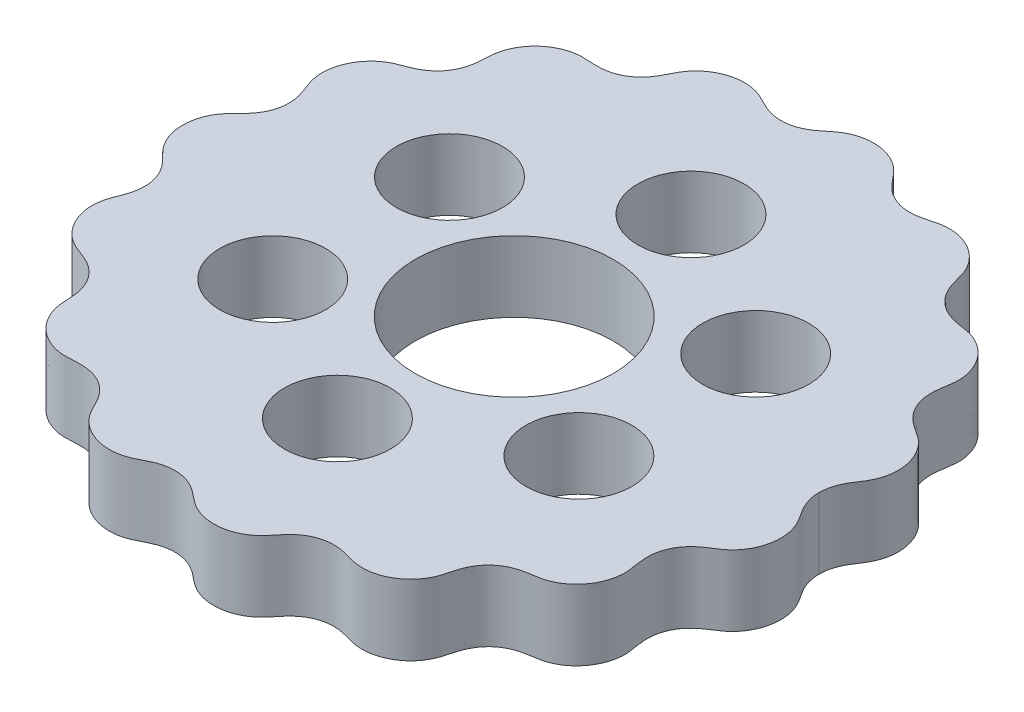
SolidWorks part; units mm, degrees
ref_plane "Front Plane" through (0, 0, 0) normal (0, 0, 1) x (1, 0, 0)
ref_plane "Top Plane" through (0, 0, 0) normal (0, 1, 0) x (1, 0, 0)
ref_plane "Right Plane" through (0, 0, 0) normal (1, 0, 0) x (0, 0, -1)
sketch "Sketch1" plane through (0, 0, 0) normal (0, 1, 0) x (1, 0, 0)
  spline S0 degree 4 poles (44.5984, 12.4944) (44.832, 12.1879) (45.2512, 11.5384) (45.7237, 10.4856) (45.9984, 9.1724) (46.03, 8.0346) (45.9105, 7.0216) (45.7203, 6.2632) (45.4573, 5.5829) (45.1464, 4.9823) (44.8648, 4.5205) (44.5648, 4.0709) (44.2669, 3.6199) (44.0083, 3.1913) (43.7929, 2.7844) (43.6185, 2.4022) (43.4802, 2.0484) (43.3629, 1.687) (43.2797, 1.3651) (43.2227, 1.0859) (43.1851, 0.8518) (43.1609, 0.6624) (43.145, 0.4992) (43.1351, 0.3578) (43.1294, 0.2322) (43.1264, 0.1298) (43.1245, 0.0125) (43.1252, -0.0782) (43.1286, -0.2195) (43.135, -0.3523) (43.1419, -0.4548) (43.1529, -0.582) (43.1699, -0.7377) (43.1951, -0.92) (43.231, -1.126) (43.274, -1.3311) (43.3366, -1.5852) (43.4549, -1.9872) (43.66, -2.5262) (44.0033, -3.2085) (44.4867, -3.963) (45.0117, -4.7244) (45.4649, -5.567) (45.8298, -6.5835) (46.0376, -7.77) (46.0189, -9.1082) (45.6992, -10.542) (45.1324, -11.7906) (44.3914, -12.8211) (43.5537, -13.6249) (42.6868, -14.2187) (41.8472, -14.7237) (41.113, -15.2701) (40.3565, -15.9849) (39.644, -16.9209) (39.0655, -18.1762) (38.8218, -19.6149) (38.8837, -20.8087) (39.0365, -21.7287) (39.15, -22.395) (39.2185, -22.9317) (39.2565, -23.6072) (39.2077, -24.5293) (38.9566, -25.6753) (38.3836, -26.9664) (37.4913, -28.188) (36.4562, -29.1122) (35.3715, -29.7513) (34.3004, -30.1449) (33.2968, -30.3406) (32.3424, -30.4567) (31.4554, -30.643) (30.6507, -30.9105) (29.9366, -31.2505) (29.1129, -31.7819) (28.2521, -32.581) (27.6169, -33.5017) (27.1961, -34.4634) (26.9571, -35.2233) (26.8167, -35.7523) (26.6832, -36.2827) (26.5312, -36.8085) (26.2971, -37.4517) (25.8833, -38.2906) (25.1883, -39.2563) (24.1248, -40.2304) (22.7782, -41.008) (21.4029, -41.4417) (20.2189, -41.5611) (19.2857, -41.4995) (18.4763, -41.358) (17.6848, -41.1398) (16.6569, -40.8411) (15.3426, -40.6571) (13.8913, -40.7732) (12.5919, -41.238) (11.5918, -41.8684) (10.8098, -42.5627) (10.2051, -43.2377) (9.6272, -44.0062) (8.9561, -44.7774) (8.0796, -45.5082) (6.9838, -46.1281) (5.6659, -46.5624) (4.1618, -46.7244) (2.7571, -46.5751) (1.6391, -46.2195) (0.8162, -45.8007) (0.2502, -45.4301) (-0.1804, -45.1024) (-0.7006, -44.671) (-1.421, -44.0787) (-2.4239, -43.4281) (-3.7917, -42.9198) (-5.168, -42.7932) (-6.3349, -42.9422) (-7.3322, -43.24) (-8.1725, -43.6026) (-9.0297, -44.0772) (-9.9774, -44.531) (-11.0923, -44.8546) (-12.3553, -44.9811) (-13.7375, -44.8459) (-15.1718, -44.3905) (-16.3918, -43.6927) (-17.2693, -42.9227) (-17.8533, -42.2132) (-18.2222, -41.6499) (-18.4839, -41.1793) (-18.7839, -40.5772) (-19.1955, -39.7455) (-19.8345, -38.7424) (-20.8622, -37.7122) (-22.2286, -36.9233) (-23.6346, -36.5484) (-24.8229, -36.4966) (-25.7489, -36.5559) (-26.4204, -36.5972) (-26.9588, -36.6058) (-27.631, -36.5681) (-28.5375, -36.417) (-29.643, -36.0421) (-30.8574, -35.3344) (-31.969, -34.32) (-32.7771, -33.1905) (-33.2991, -32.0336) (-33.5763, -30.9061) (-33.6571, -29.8585) (-33.6747, -28.8788) (-33.7808, -27.9699) (-34.0216, -26.9573) (-34.476, -25.8723) (-35.2738, -24.7436) (-36.3979, -23.8132) (-37.4628, -23.2699) (-38.3359, -22.9423) (-38.9696, -22.7074) (-39.4687, -22.4983) (-40.0727, -22.1935) (-40.8469, -21.6902) (-41.7138, -20.8998) (-42.5454, -19.758) (-43.1572, -18.3744) (-43.44, -17.0159) (-43.4511, -15.757) (-43.2564, -14.6325) (-42.9241, -13.6656) (-42.5475, -12.7809) (-42.2653, -11.9197) (-42.055, -10.8955) (-42.0167, -9.9082) (-42.1512, -8.933) (-42.4518, -8.0043) (-42.7822, -7.3039) (-43.24, -6.5824) (-43.8372, -5.8614) (-44.4706, -5.2544) (-45.0553, -4.6782) (-45.4944, -4.1525) (-45.8114, -3.7063) (-46.0684, -3.2686) (-46.2741, -2.8497) (-46.4358, -2.4552) (-46.5617, -2.0905) (-46.6535, -1.7655) (-46.7191, -1.4838) (-46.7651, -1.2471) (-46.7966, -1.0568) (-46.8229, -0.866) (-46.8439, -0.6732) (-46.8577, -0.507) (-46.8662, -0.3636) (-46.8712, -0.2362) (-46.8738, -0.132) (-46.8754, -0.0158) (-46.8748, 0.091) (-46.8703, 0.2911) (-46.8602, 0.4745) (-46.8449, 0.6629) (-46.8245, 0.8522) (-46.7991, 1.0403) (-46.7685, 1.2276) (-46.724, 1.4607) (-46.6604, 1.7382) (-46.5715, 2.0584) (-46.4496, 2.4181) (-46.2927, 2.8077) (-46.0929, 3.2223) (-45.843, 3.6565) (-45.5342, 4.1002) (-45.1056, 4.6236) (-44.5323, 5.1972) (-43.9, 5.7965) (-43.2951, 6.5085) (-42.8248, 7.2269) (-42.4804, 7.9319) (-42.1599, 8.8828) (-42.0135, 9.8922) (-42.0547, 10.922) (-42.228, 11.7337) (-42.3436, 12.1315) (-42.4074, 12.3284) knots 0 0 0 0 0 0.008419 0.016837 0.025005 0.029089 0.033173 0.039077 0.042029 0.044981 0.047933 0.050885 0.053837 0.056789 0.058863 0.060937 0.063011 0.065085 0.067158 0.068195 0.069232 0.070269 0.071306 0.071825 0.072343 0.072861 0.07338 0.074472 0.075017 0.075563 0.076135 0.076707 0.07785 0.078994 0.080138 0.081281 0.082425 0.084712 0.089287 0.093861 0.099069 0.104277 0.109486 0.114694 0.122573 0.130452 0.138512 0.146571 0.152296 0.158021 0.163745 0.16947 0.173713 0.177956 0.186442 0.195001 0.203561 0.209467 0.212421 0.215374 0.218327 0.22128 0.227187 0.235488 0.24379 0.251894 0.259998 0.265567 0.271137 0.276706 0.282275 0.286582 0.290889 0.295197 0.299504 0.307939 0.316375 0.319362 0.32235 0.325338 0.328326 0.331314 0.334302 0.340277 0.348703 0.357129 0.365555 0.373981 0.379956 0.382944 0.385932 0.391908 0.397883 0.406319 0.414754 0.423368 0.427675 0.431982 0.437552 0.443121 0.44869 0.45426 0.462364 0.470468 0.478769 0.487071 0.492978 0.495931 0.498884 0.501837 0.50479 0.510697 0.519257 0.527816 0.536302 0.540545 0.544788 0.550513 0.556237 0.561962 0.567686 0.575746 0.583806 0.592068 0.60033 0.606208 0.609147 0.612086 0.615025 0.617964 0.623842 0.63236 0.640878 0.649396 0.657914 0.663792 0.666731 0.66967 0.672609 0.675548 0.681426 0.689688 0.69795 0.70601 0.714069 0.719794 0.725519 0.731243 0.736968 0.741211 0.745454 0.75394 0.762499 0.771059 0.776965 0.779919 0.782872 0.785825 0.788778 0.794685 0.802986 0.811288 0.819392 0.827496 0.833065 0.838635 0.844204 0.849773 0.85408 0.858388 0.867002 0.871219 0.875437 0.879655 0.883873 0.889848 0.895824 0.898812 0.9018 0.904787 0.907775 0.909882 0.911988 0.914095 0.916201 0.917254 0.918308 0.919361 0.920414 0.921467 0.92252 0.923047 0.923574 0.9241 0.924627 0.925664 0.9267 0.927737 0.928773 0.92981 0.930846 0.931883 0.93292 0.934993 0.937066 0.939139 0.941212 0.944163 0.947114 0.950065 0.953016 0.958918 0.96482 0.969093 0.973365 0.977638 0.981911 0.990955 0.995478 1 1 1 1 1 construction
  spline S1 degree 4 poles (43.125, 0) (43.125, -0.0425) (43.1258, -0.1053) (43.1286, -0.2195) (43.135, -0.3523) (43.1419, -0.4548) (43.1529, -0.582) (43.1699, -0.7377) (43.1951, -0.92) (43.231, -1.126) (43.274, -1.3311) (43.3366, -1.5852) (43.4549, -1.9872) (43.66, -2.5262) (44.0033, -3.2085) (44.4867, -3.963) (45.0117, -4.7244) (45.4649, -5.567) (45.8298, -6.5835) (46.0376, -7.77) (46.0189, -9.1082) (45.6992, -10.542) (45.1324, -11.7906) (44.3914, -12.8211) (43.5537, -13.6249) (42.6868, -14.2187) (41.8472, -14.7237) (41.113, -15.2701) (40.3565, -15.9849) (39.644, -16.9209) (39.0655, -18.1762) (38.8218, -19.6149) (38.8837, -20.8087) (39.0365, -21.7287) (39.15, -22.395) (39.2185, -22.9317) (39.2565, -23.6072) (39.2077, -24.5293) (38.9566, -25.6753) (38.3836, -26.9664) (37.4913, -28.188) (36.4562, -29.1122) (35.3715, -29.7513) (34.3004, -30.1449) (33.2968, -30.3406) (32.3424, -30.4567) (31.4554, -30.643) (30.6507, -30.9105) (29.9366, -31.2505) (29.1129, -31.7819) (28.2521, -32.581) (27.6169, -33.5017) (27.1961, -34.4634) (26.9571, -35.2233) (26.8167, -35.7523) (26.6832, -36.2827) (26.5312, -36.8085) (26.2971, -37.4517) (25.8833, -38.2906) (25.1883, -39.2563) (24.1248, -40.2304) (22.7782, -41.008) (21.4029, -41.4417) (20.2189, -41.5611) (19.2857, -41.4995) (18.4763, -41.358) (17.6848, -41.1398) (16.6569, -40.8411) (15.3426, -40.6571) (13.8913, -40.7732) (12.5919, -41.238) (11.5918, -41.8684) (10.8098, -42.5627) (10.2051, -43.2377) (9.6272, -44.0062) (8.9561, -44.7774) (8.0796, -45.5082) (6.9838, -46.1281) (5.6659, -46.5624) (4.1618, -46.7244) (2.7571, -46.5751) (1.6391, -46.2195) (0.8162, -45.8007) (0.2502, -45.4301) (-0.1804, -45.1024) (-0.7006, -44.671) (-1.421, -44.0787) (-2.4239, -43.4281) (-3.7917, -42.9198) (-5.168, -42.7932) (-6.3349, -42.9422) (-7.3322, -43.24) (-8.1725, -43.6026) (-9.0297, -44.0772) (-9.9774, -44.531) (-11.0923, -44.8546) (-12.3553, -44.9811) (-13.7375, -44.8459) (-15.1718, -44.3905) (-16.3918, -43.6927) (-17.2693, -42.9227) (-17.8533, -42.2132) (-18.2222, -41.6499) (-18.4839, -41.1793) (-18.7839, -40.5772) (-19.1955, -39.7455) (-19.8345, -38.7424) (-20.8622, -37.7122) (-22.2286, -36.9233) (-23.6346, -36.5484) (-24.8229, -36.4966) (-25.7489, -36.5559) (-26.4204, -36.5972) (-26.9588, -36.6058) (-27.631, -36.5681) (-28.5375, -36.417) (-29.643, -36.0421) (-30.8574, -35.3344) (-31.969, -34.32) (-32.7771, -33.1905) (-33.2991, -32.0336) (-33.5763, -30.9061) (-33.6571, -29.8585) (-33.6747, -28.8788) (-33.7808, -27.9699) (-34.0216, -26.9573) (-34.476, -25.8723) (-35.2738, -24.7436) (-36.3979, -23.8132) (-37.4628, -23.2699) (-38.3359, -22.9423) (-38.9696, -22.7074) (-39.4687, -22.4983) (-40.0727, -22.1935) (-40.8469, -21.6902) (-41.7138, -20.8998) (-42.5454, -19.758) (-43.1572, -18.3744) (-43.44, -17.0159) (-43.4511, -15.757) (-43.2564, -14.6325) (-42.9241, -13.6656) (-42.5475, -12.7809) (-42.2653, -11.9197) (-42.055, -10.8955) (-42.0167, -9.9082) (-42.1512, -8.933) (-42.4518, -8.0043) (-42.7822, -7.3039) (-43.24, -6.5824) (-43.8372, -5.8614) (-44.4706, -5.2544) (-45.0553, -4.6782) (-45.4944, -4.1525) (-45.8114, -3.7063) (-46.0684, -3.2686) (-46.2741, -2.8497) (-46.4358, -2.4552) (-46.5617, -2.0905) (-46.6535, -1.7655) (-46.7191, -1.4838) (-46.7651, -1.2471) (-46.7966, -1.0568) (-46.8229, -0.866) (-46.8439, -0.6732) (-46.8577, -0.507) (-46.8662, -0.3636) (-46.8712, -0.2362) (-46.8738, -0.132) (-46.8748, -0.0619) (-46.875, -0.0205) (-46.875, 0) knots 0.07338 0.07338 0.07338 0.07338 0.07338 0.074472 0.075017 0.075563 0.076135 0.076707 0.07785 0.078994 0.080138 0.081281 0.082425 0.084712 0.089287 0.093861 0.099069 0.104277 0.109486 0.114694 0.122573 0.130452 0.138512 0.146571 0.152296 0.158021 0.163745 0.16947 0.173713 0.177956 0.186442 0.195001 0.203561 0.209467 0.212421 0.215374 0.218327 0.22128 0.227187 0.235488 0.24379 0.251894 0.259998 0.265567 0.271137 0.276706 0.282275 0.286582 0.290889 0.295197 0.299504 0.307939 0.316375 0.319362 0.32235 0.325338 0.328326 0.331314 0.334302 0.340277 0.348703 0.357129 0.365555 0.373981 0.379956 0.382944 0.385932 0.391908 0.397883 0.406319 0.414754 0.423368 0.427675 0.431982 0.437552 0.443121 0.44869 0.45426 0.462364 0.470468 0.478769 0.487071 0.492978 0.495931 0.498884 0.501837 0.50479 0.510697 0.519257 0.527816 0.536302 0.540545 0.544788 0.550513 0.556237 0.561962 0.567686 0.575746 0.583806 0.592068 0.60033 0.606208 0.609147 0.612086 0.615025 0.617964 0.623842 0.63236 0.640878 0.649396 0.657914 0.663792 0.666731 0.66967 0.672609 0.675548 0.681426 0.689688 0.69795 0.70601 0.714069 0.719794 0.725519 0.731243 0.736968 0.741211 0.745454 0.75394 0.762499 0.771059 0.776965 0.779919 0.782872 0.785825 0.788778 0.794685 0.802986 0.811288 0.819392 0.827496 0.833065 0.838635 0.844204 0.849773 0.85408 0.858388 0.867002 0.871219 0.875437 0.879655 0.883873 0.889848 0.895824 0.898812 0.9018 0.904787 0.907775 0.909882 0.911988 0.914095 0.916201 0.917254 0.918308 0.919361 0.920414 0.921467 0.92252 0.923047 0.923574 0.9241 0.924627 0.924627 0.924627 0.924627 0.924627
  spline S2 degree 4 poles (43.125, 0) (43.125, 0.0425) (43.1258, 0.1053) (43.1286, 0.2195) (43.135, 0.3523) (43.1419, 0.4548) (43.1529, 0.582) (43.1699, 0.7377) (43.1951, 0.92) (43.231, 1.126) (43.274, 1.3311) (43.3366, 1.5852) (43.4549, 1.9872) (43.66, 2.5262) (44.0033, 3.2085) (44.4867, 3.963) (45.0117, 4.7244) (45.4649, 5.567) (45.8298, 6.5835) (46.0376, 7.77) (46.0189, 9.1082) (45.6992, 10.542) (45.1324, 11.7906) (44.3914, 12.8211) (43.5537, 13.6249) (42.6868, 14.2187) (41.8472, 14.7237) (41.113, 15.2701) (40.3565, 15.9849) (39.644, 16.9209) (39.0655, 18.1762) (38.8218, 19.6149) (38.8837, 20.8087) (39.0365, 21.7287) (39.15, 22.395) (39.2185, 22.9317) (39.2565, 23.6072) (39.2077, 24.5293) (38.9566, 25.6753) (38.3836, 26.9664) (37.4913, 28.188) (36.4562, 29.1122) (35.3715, 29.7513) (34.3004, 30.1449) (33.2968, 30.3406) (32.3424, 30.4567) (31.4554, 30.643) (30.6507, 30.9105) (29.9366, 31.2505) (29.1129, 31.7819) (28.2521, 32.581) (27.6169, 33.5017) (27.1961, 34.4634) (26.9571, 35.2233) (26.8167, 35.7523) (26.6832, 36.2827) (26.5312, 36.8085) (26.2971, 37.4517) (25.8833, 38.2906) (25.1883, 39.2563) (24.1248, 40.2304) (22.7782, 41.008) (21.4029, 41.4417) (20.2189, 41.5611) (19.2857, 41.4995) (18.4763, 41.358) (17.6848, 41.1398) (16.6569, 40.8411) (15.3426, 40.6571) (13.8913, 40.7732) (12.5919, 41.238) (11.5918, 41.8684) (10.8098, 42.5627) (10.2051, 43.2377) (9.6272, 44.0062) (8.9561, 44.7774) (8.0796, 45.5082) (6.9838, 46.1281) (5.6659, 46.5624) (4.1618, 46.7244) (2.7571, 46.5751) (1.6391, 46.2195) (0.8162, 45.8007) (0.2502, 45.4301) (-0.1804, 45.1024) (-0.7006, 44.671) (-1.421, 44.0787) (-2.4239, 43.4281) (-3.7917, 42.9198) (-5.168, 42.7932) (-6.3349, 42.9422) (-7.3322, 43.24) (-8.1725, 43.6026) (-9.0297, 44.0772) (-9.9774, 44.531) (-11.0923, 44.8546) (-12.3553, 44.9811) (-13.7375, 44.8459) (-15.1718, 44.3905) (-16.3918, 43.6927) (-17.2693, 42.9227) (-17.8533, 42.2132) (-18.2222, 41.6499) (-18.4839, 41.1793) (-18.7839, 40.5772) (-19.1955, 39.7455) (-19.8345, 38.7424) (-20.8622, 37.7122) (-22.2286, 36.9233) (-23.6346, 36.5484) (-24.8229, 36.4966) (-25.7489, 36.5559) (-26.4204, 36.5972) (-26.9588, 36.6058) (-27.631, 36.5681) (-28.5375, 36.417) (-29.643, 36.0421) (-30.8574, 35.3344) (-31.969, 34.32) (-32.7771, 33.1905) (-33.2991, 32.0336) (-33.5763, 30.9061) (-33.6571, 29.8585) (-33.6747, 28.8788) (-33.7808, 27.9699) (-34.0216, 26.9573) (-34.476, 25.8723) (-35.2738, 24.7436) (-36.3979, 23.8132) (-37.4628, 23.2699) (-38.3359, 22.9423) (-38.9696, 22.7074) (-39.4687, 22.4983) (-40.0727, 22.1935) (-40.8469, 21.6902) (-41.7138, 20.8998) (-42.5454, 19.758) (-43.1572, 18.3744) (-43.44, 17.0159) (-43.4511, 15.757) (-43.2564, 14.6325) (-42.9241, 13.6656) (-42.5475, 12.7809) (-42.2653, 11.9197) (-42.055, 10.8955) (-42.0167, 9.9082) (-42.1512, 8.933) (-42.4518, 8.0043) (-42.7822, 7.3039) (-43.24, 6.5824) (-43.8372, 5.8614) (-44.4706, 5.2544) (-45.0553, 4.6782) (-45.4944, 4.1525) (-45.8114, 3.7063) (-46.0684, 3.2686) (-46.2741, 2.8497) (-46.4358, 2.4552) (-46.5617, 2.0905) (-46.6535, 1.7655) (-46.7191, 1.4838) (-46.7651, 1.2471) (-46.7966, 1.0568) (-46.8229, 0.866) (-46.8439, 0.6732) (-46.8577, 0.507) (-46.8662, 0.3636) (-46.8712, 0.2362) (-46.8738, 0.132) (-46.8748, 0.0619) (-46.875, 0.0205) (-46.875, 0) knots 0.07338 0.07338 0.07338 0.07338 0.07338 0.074472 0.075017 0.075563 0.076135 0.076707 0.07785 0.078994 0.080138 0.081281 0.082425 0.084712 0.089287 0.093861 0.099069 0.104277 0.109486 0.114694 0.122573 0.130452 0.138512 0.146571 0.152296 0.158021 0.163745 0.16947 0.173713 0.177956 0.186442 0.195001 0.203561 0.209467 0.212421 0.215374 0.218327 0.22128 0.227187 0.235488 0.24379 0.251894 0.259998 0.265567 0.271137 0.276706 0.282275 0.286582 0.290889 0.295197 0.299504 0.307939 0.316375 0.319362 0.32235 0.325338 0.328326 0.331314 0.334302 0.340277 0.348703 0.357129 0.365555 0.373981 0.379956 0.382944 0.385932 0.391908 0.397883 0.406319 0.414754 0.423368 0.427675 0.431982 0.437552 0.443121 0.44869 0.45426 0.462364 0.470468 0.478769 0.487071 0.492978 0.495931 0.498884 0.501837 0.50479 0.510697 0.519257 0.527816 0.536302 0.540545 0.544788 0.550513 0.556237 0.561962 0.567686 0.575746 0.583806 0.592068 0.60033 0.606208 0.609147 0.612086 0.615025 0.617964 0.623842 0.63236 0.640878 0.649396 0.657914 0.663792 0.666731 0.66967 0.672609 0.675548 0.681426 0.689688 0.69795 0.70601 0.714069 0.719794 0.725519 0.731243 0.736968 0.741211 0.745454 0.75394 0.762499 0.771059 0.776965 0.779919 0.782872 0.785825 0.788778 0.794685 0.802986 0.811288 0.819392 0.827496 0.833065 0.838635 0.844204 0.849773 0.85408 0.858388 0.867002 0.871219 0.875437 0.879655 0.883873 0.889848 0.895824 0.898812 0.9018 0.904787 0.907775 0.909882 0.911988 0.914095 0.916201 0.917254 0.918308 0.919361 0.920414 0.921467 0.92252 0.923047 0.923574 0.9241 0.924627 0.924627 0.924627 0.924627 0.924627
extrude "Boss-Extrude1" add sketch "Sketch1" along normal blind 10 contours S2 S1
sketch "Sketch2" plane through (0, 10, 0) normal (0, 1, 0) x (1, 0, 0)
  circle A0 centre (0, 0) radius 14
  circle A1 centre (0, 25) radius 7.5
  circle A7 centre (21.6506, 12.5) radius 7.5
  circle A8 centre (21.6506, -12.5) radius 7.5
  circle A9 centre (0, -25) radius 7.5
  circle A10 centre (-21.6506, -12.5) radius 7.5
  circle A11 centre (-21.6506, 12.5) radius 7.5
  point P17 (4.3301, -2.5)
  point P18 (0, 0)
  dimension "D1" = 28
  dimension "D2" = 15
  dimension "D3" = 25
  dimension "D4" = 6
extrude "Cut-Extrude1" cut sketch "Sketch2" against normal blind 10
